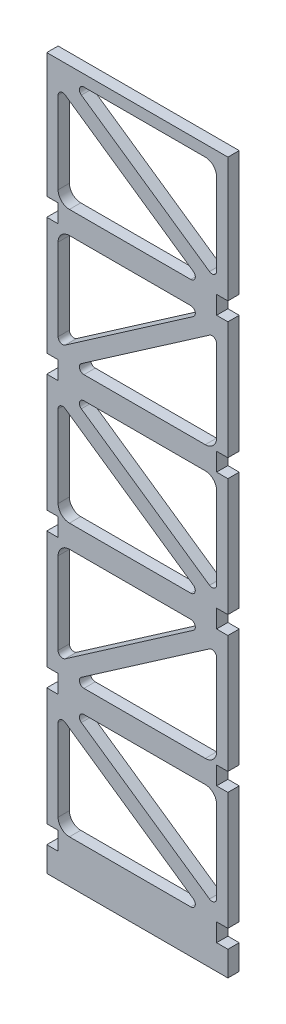
SolidWorks part; units mm, degrees
material "Balsa"
ref_plane "Front Plane" through (0, 0, 0) normal (0, 0, 1) x (1, 0, 0)
ref_plane "Top Plane" through (0, 0, 0) normal (0, 1, 0) x (1, 0, 0)
ref_plane "Right Plane" through (0, 0, 0) normal (1, 0, 0) x (0, 0, -1)
sketch "Model" plane through (0, 0, 0) normal (0, 0, 1) x (1, 0, 0)
  line L0 (88.9, 87.63) -> (20.8312, 87.63)
  line L1 (95.25, 35.3278) -> (95.25, 81.28)
  line L2 (19.3854, 83.0016) -> (91.2642, 33.2394)
  line L3 (6.35, 157.48) -> (6.35, 111.5278)
  line L4 (80.7688, 163.83) -> (12.7, 163.83)
  line L5 (10.3358, 109.4394) -> (82.2146, 159.2016)
  line L6 (88.9, 240.03) -> (20.8312, 240.03)
  line L7 (95.25, 187.7278) -> (95.25, 233.68)
  line L8 (19.3854, 235.4016) -> (91.2642, 185.6394)
  line L9 (12.7, 176.53) -> (80.7688, 176.53)
  line L10 (6.35, 228.8322) -> (6.35, 182.88)
  line L11 (82.2146, 181.1584) -> (10.3358, 230.9206)
  line L12 (91.2642, 154.7206) -> (19.3854, 104.9584)
  line L13 (95.25, 106.68) -> (95.25, 152.6322)
  line L14 (20.8312, 100.33) -> (88.9, 100.33)
  line L15 (6.35, 309.88) -> (6.35, 263.9278)
  line L16 (80.7688, 316.23) -> (12.7, 316.23)
  line L17 (10.3358, 261.8394) -> (82.2146, 311.6016)
  line L18 (88.9, 392.43) -> (20.8312, 392.43)
  line L19 (95.25, 340.1278) -> (95.25, 386.08)
  line L20 (19.3854, 387.8016) -> (91.2642, 338.0394)
  line L21 (12.7, 328.93) -> (80.7688, 328.93)
  line L22 (6.35, 381.2322) -> (6.35, 335.28)
  line L23 (82.2146, 333.5584) -> (10.3358, 383.3206)
  line L24 (12.7, 24.13) -> (80.7688, 24.13)
  line L25 (6.35, 76.4322) -> (6.35, 30.48)
  line L26 (82.2146, 28.7584) -> (10.3358, 78.5206)
  line L27 (91.2642, 307.1206) -> (19.3854, 257.3584)
  line L28 (95.25, 259.08) -> (95.25, 305.0322)
  line L29 (20.8312, 252.73) -> (88.9, 252.73)
  line L30 (0, 398.78) -> (0, 0)
  line L31 (0, 0) -> (101.6, 0)
  line L32 (101.6, 398.78) -> (101.6, 0)
  line L33 (0, 398.78) -> (101.6, 398.78)
  arc A0 (95.25, 81.28) -> (88.9, 87.63) centre (88.9, 81.28) ccw
  arc A1 (91.2642, 33.2394) -> (95.25, 35.3278) centre (92.71, 35.3278) ccw
  arc A2 (20.8312, 87.63) -> (19.3854, 83.0016) centre (20.8312, 85.09) ccw
  arc A3 (12.7, 163.83) -> (6.35, 157.48) centre (12.7, 157.48) ccw
  arc A4 (82.2146, 159.2016) -> (80.7688, 163.83) centre (80.7688, 161.29) ccw
  arc A5 (6.35, 111.5278) -> (10.3358, 109.4394) centre (8.89, 111.5278) ccw
  arc A6 (95.25, 233.68) -> (88.9, 240.03) centre (88.9, 233.68) ccw
  arc A7 (91.2642, 185.6394) -> (95.25, 187.7278) centre (92.71, 187.7278) ccw
  arc A8 (20.8312, 240.03) -> (19.3854, 235.4016) centre (20.8312, 237.49) ccw
  arc A9 (6.35, 182.88) -> (12.7, 176.53) centre (12.7, 182.88) ccw
  arc A10 (10.3358, 230.9206) -> (6.35, 228.8322) centre (8.89, 228.8322) ccw
  arc A11 (80.7688, 176.53) -> (82.2146, 181.1584) centre (80.7688, 179.07) ccw
  arc A12 (95.25, 152.6322) -> (91.2642, 154.7206) centre (92.71, 152.6322) ccw
  arc A13 (88.9, 100.33) -> (95.25, 106.68) centre (88.9, 106.68) ccw
  arc A14 (19.3854, 104.9584) -> (20.8312, 100.33) centre (20.8312, 102.87) ccw
  arc A15 (12.7, 316.23) -> (6.35, 309.88) centre (12.7, 309.88) ccw
  arc A16 (82.2146, 311.6016) -> (80.7688, 316.23) centre (80.7688, 313.69) ccw
  arc A17 (6.35, 263.9278) -> (10.3358, 261.8394) centre (8.89, 263.9278) ccw
  arc A18 (95.25, 386.08) -> (88.9, 392.43) centre (88.9, 386.08) ccw
  arc A19 (91.2642, 338.0394) -> (95.25, 340.1278) centre (92.71, 340.1278) ccw
  arc A20 (20.8312, 392.43) -> (19.3854, 387.8016) centre (20.8312, 389.89) ccw
  arc A21 (6.35, 335.28) -> (12.7, 328.93) centre (12.7, 335.28) ccw
  arc A22 (10.3358, 383.3206) -> (6.35, 381.2322) centre (8.89, 381.2322) ccw
  arc A23 (80.7688, 328.93) -> (82.2146, 333.5584) centre (80.7688, 331.47) ccw
  arc A24 (6.35, 30.48) -> (12.7, 24.13) centre (12.7, 30.48) ccw
  arc A25 (10.3358, 78.5206) -> (6.35, 76.4322) centre (8.89, 76.4322) ccw
  arc A26 (80.7688, 24.13) -> (82.2146, 28.7584) centre (80.7688, 26.67) ccw
  arc A27 (95.25, 305.0322) -> (91.2642, 307.1206) centre (92.71, 305.0322) ccw
  arc A28 (88.9, 252.73) -> (95.25, 259.08) centre (88.9, 259.08) ccw
  arc A29 (19.3854, 257.3584) -> (20.8312, 252.73) centre (20.8312, 255.27) ccw
extrude "Boss-Extrude1" add sketch "Model" along normal blind 6.35
sketch "Sketch1" plane through (0, 0, 6.35) normal (0, 0, 1) x (1, 0, 0)
  line L0 (101.6, 0) -> (101.6, 398.78) construction
  line L1 (101.6, 328.93) -> (95.25, 328.93)
  line L2 (101.6, 328.93) -> (101.6, 318.77)
  line L3 (101.6, 318.77) -> (95.25, 318.77)
  line L4 (95.25, 328.93) -> (95.25, 318.77)
  line L5 (0, 398.78) -> (0, 0) construction
  line L6 (0, 252.73) -> (6.35, 252.73)
  line L7 (0, 252.73) -> (0, 242.57)
  line L8 (0, 242.57) -> (6.35, 242.57)
  line L9 (6.35, 252.73) -> (6.35, 242.57)
  line L10 (12.7, 328.93) -> (80.7688, 328.93) construction
  line L11 (101.6, 176.53) -> (95.25, 176.53)
  line L12 (101.6, 176.53) -> (101.6, 166.37)
  line L13 (101.6, 166.37) -> (95.25, 166.37)
  line L14 (95.25, 176.53) -> (95.25, 166.37)
  line L15 (0, 100.33) -> (6.35, 100.33)
  line L16 (0, 100.33) -> (0, 90.17)
  line L17 (0, 90.17) -> (6.35, 90.17)
  line L18 (6.35, 100.33) -> (6.35, 90.17)
  line L19 (20.8312, 252.73) -> (88.9, 252.73) construction
  line L20 (12.7, 176.53) -> (80.7688, 176.53) construction
  line L21 (20.8312, 100.33) -> (88.9, 100.33) construction
  line L22 (12.7, 24.13) -> (80.7688, 24.13) construction
  line L23 (0, 328.93) -> (6.35, 328.93)
  line L24 (0, 328.93) -> (0, 318.77)
  line L25 (0, 318.77) -> (6.35, 318.77)
  line L26 (6.35, 328.93) -> (6.35, 318.77)
  line L27 (101.6, 252.73) -> (95.25, 252.73)
  line L28 (101.6, 252.73) -> (101.6, 242.57)
  line L29 (101.6, 242.57) -> (95.25, 242.57)
  line L30 (95.25, 252.73) -> (95.25, 242.57)
  line L31 (0, 176.53) -> (6.35, 176.53)
  line L32 (0, 176.53) -> (0, 166.37)
  line L33 (0, 166.37) -> (6.35, 166.37)
  line L34 (6.35, 176.53) -> (6.35, 166.37)
  line L35 (101.6, 100.33) -> (95.25, 100.33)
  line L36 (101.6, 100.33) -> (101.6, 90.17)
  line L37 (101.6, 90.17) -> (95.25, 90.17)
  line L38 (95.25, 100.33) -> (95.25, 90.17)
  line L39 (0, 24.13) -> (6.35, 24.13)
  line L40 (0, 24.13) -> (0, 13.97)
  line L41 (0, 13.97) -> (6.35, 13.97)
  line L42 (6.35, 24.13) -> (6.35, 13.97)
  line L43 (101.6, 24.13) -> (95.25, 24.13)
  line L44 (101.6, 24.13) -> (101.6, 13.97)
  line L45 (101.6, 13.97) -> (95.25, 13.97)
  line L46 (95.25, 24.13) -> (95.25, 13.97)
  dimension "D1" = 6.35
  dimension "D2" = 10.16
  dimension "D3" = 10.16
  dimension "D4" = 6.35
  dimension "D5" = 6.35
  dimension "D6" = 10.16
  dimension "D7" = 6.35
  dimension "D8" = 10.16
  dimension "D9" = 10.16
  dimension "D10" = 10.16
extrude "Cut-Extrude1" cut sketch "Sketch1" against normal up to surface (6.35 mm away) up to face at (50.8, 199.39, 0)
equation "\"thick\"=0.25"
equation "\"D1@Boss-Extrude1\"=\"thick\""
